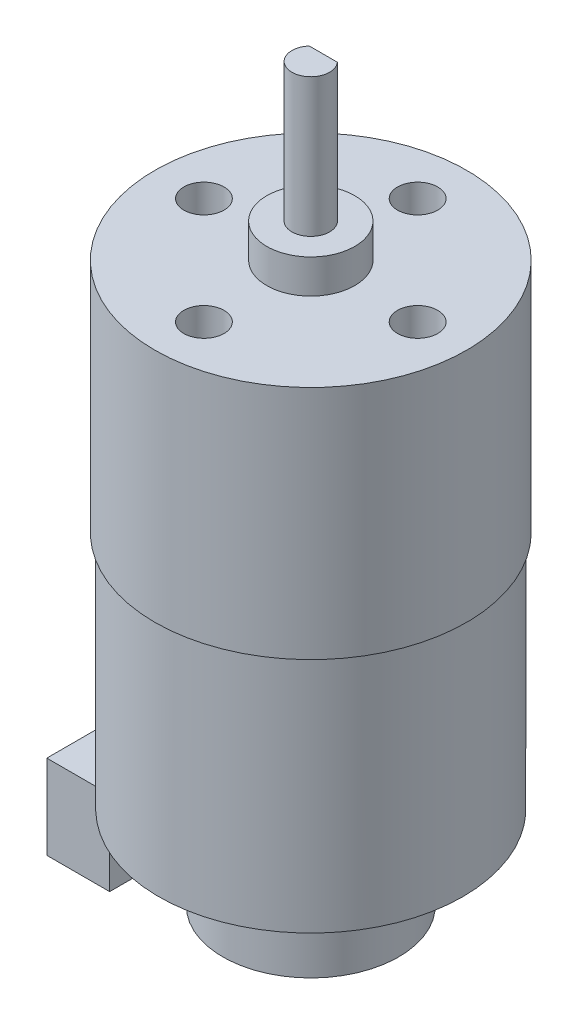
SolidWorks part; units mm, degrees
ref_plane "前视基准面" through (0, 0, 0) normal (0, 0, 1) x (1, 0, 0)
ref_plane "上视基准面" through (0, 0, 0) normal (0, 1, 0) x (1, 0, 0)
ref_plane "右视基准面" through (0, 0, 0) normal (1, 0, 0) x (0, 0, -1)
sketch "草图2" plane through (0, 0, 0) normal (0, 1, 0) x (1, 0, 0)
  circle A0 centre (0, 0) radius 12.1
  circle A1 centre (0, 0) radius 12.4
  circle A2 centre (0, 0) radius 3.5
  circle A3 centre (0, 0) radius 1.5
  dimension "D1" = 24.2
  dimension "D2" = 24.8
  dimension "D3" = 7
  dimension "D4" = 3
extrude "凸台-拉伸1" add sketch "草图2" along normal blind 19.05 contours A0 A2 | A2 A3 | A2 | A3 | A0 region at (-11.7578, 0, 0) region at (-3.401, 0, 0)
extrude "凸台-拉伸2" add sketch "草图2<3>" along normal blind 18.75 from surface contours A1 A0 | A0 A2 | A2 A3 | A3 region at (-11.7578, 0, 0) region at (-12.3649, 0, 0) region at (-3.401, 0, 0) region at (0, 0, 0) starting at face at (0, 19.05, 12.1)
sketch "草图2<3>" plane through (0, 0, 0) normal (0, 1, 0) x (1, 0, 0) same geometry as "草图2"
extrude "凸台-拉伸3" add sketch "草图2<4>" along normal blind 2.7 from surface contours A2 A3 | A3 region at (-3.401, 0, 0) region at (0, 0, 0) starting at face at (0, 37.8, 12.4)
sketch "草图2<4>" plane through (0, 0, 0) normal (0, 1, 0) x (1, 0, 0) same geometry as "草图2"
extrude "凸台-拉伸4" add sketch "草图2<5>" along normal blind 11 from surface contours A3 region at (0, 0, 0) starting at face at (0, 40.5, 3.5)
sketch "草图2<5>" plane through (0, 0, 0) normal (0, 1, 0) x (1, 0, 0) same geometry as "草图2"
sketch "草图4" plane through (0, 37.8, 0) normal (0, 1, 0) x (1, 0, 0)
  line L0 (0, 0) -> (0, 8.5) construction
  circle A0 centre (0, 8.5) radius 1.6
  circle A1 centre (8.5, 0) radius 1.6
  circle A2 centre (0, -8.5) radius 1.6
  circle A3 centre (-8.5, 0) radius 1.6
  point P13 (0, 0)
  dimension "D1" = 3.2
  dimension "D2" = 8.5
  dimension "D3" = 4
extrude "切除-拉伸1" cut sketch "草图4" against normal blind 7 contours A0 | A3 | A2 | A1
sketch "草图5" plane through (0, 51.5, 0) normal (0, 1, 0) x (1, 0, 0)
  line L0 (0, 0) -> (0, 2) construction
  line L1 (-2.5618, 1) -> (2.5618, 1)
  line L2 (-2.5618, 1) -> (-2.5618, 2)
  line L3 (-2.5618, 2) -> (2.5618, 2)
  line L4 (2.5618, 1) -> (2.5618, 2)
  line L5 (-2.5618, 1) -> (2.5618, 2) construction
  line L6 (-2.5618, 2) -> (2.5618, 1) construction
  circle A0 centre (0, 0) radius 1.5 construction
  circle A1 centre (0, 0) radius 1.5 construction
  point P0 (0, 1.5)
  dimension "D1" = 0.5
extrude "切除-拉伸2" cut sketch "草图5" against normal blind 8
sketch "草图6" plane through (0, 0, 0) normal (0, -1, 0) x (1, 0, 0)
  line L0 (0, 0) -> (-12.4, 0) construction
  line L2 (-9, -7) -> (-14, -7)
  line L3 (-9, -7) -> (-9, 7)
  line L4 (-9, 7) -> (-14, 7)
  line L5 (-14, -7) -> (-14, 7)
  line L6 (-9, -7) -> (-14, 7) construction
  line L7 (-9, 7) -> (-14, -7) construction
  circle A0 centre (0, 0) radius 7
  circle A1 centre (0, 0) radius 12.4 construction
  point P3 (-11.5, 0)
  point P12 (0, 0)
  dimension "D1" = 14
  dimension "D2" = 14
  dimension "D3" = 5
  dimension "D4" = 9
extrude "凸台-拉伸5" add sketch "草图6" along normal blind 6.7
